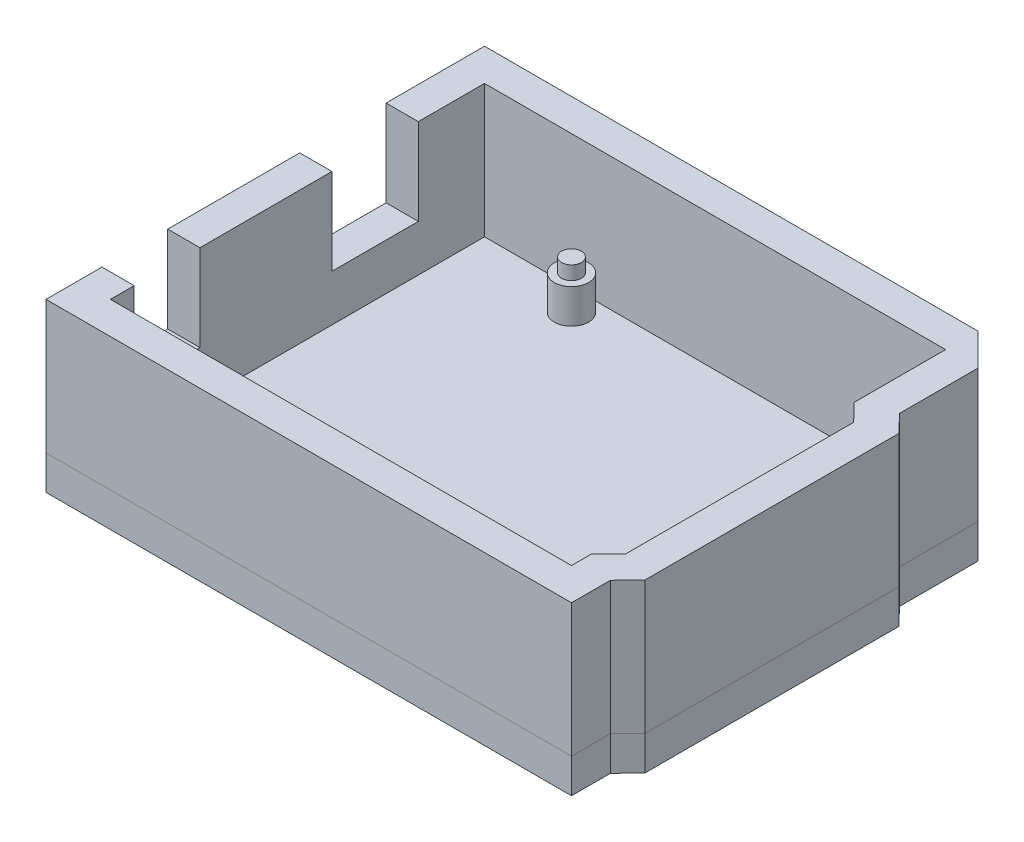
SolidWorks part; units mm, degrees
ref_plane "Front Plane" through (0, 0, 0) normal (0, 0, 1) x (1, 0, 0)
ref_plane "Top Plane" through (0, 0, 0) normal (0, 1, 0) x (1, 0, 0)
ref_plane "Right Plane" through (0, 0, 0) normal (1, 0, 0) x (0, 0, -1)
sketch "Sketch2" plane through (0, 0, 0) normal (0, 1, 0) x (1, 0, 0)
  line L3 (12.5897, 24.8031) -> (15.0697, 22.2631)
  line L4 (15.0697, 22.2631) -> (15.0697, -10.5029)
  line L5 (15.0697, -10.5029) -> (12.5897, -13.0429)
  line L6 (12.5897, -13.0429) -> (12.5897, -15.5829)
  line L7 (12.5897, -15.5829) -> (-53.4803, -15.5829)
  line L8 (-53.4803, -15.5829) -> (-53.4803, 37.7956)
  line L9 (-58.7803, 43.0956) -> (13.2202, 43.0956)
  line L10 (13.2202, 43.0956) -> (17.8897, 38.4261)
  line L11 (17.8897, 38.4261) -> (17.8897, 26.9614)
  line L12 (17.8897, 26.9614) -> (20.3697, 24.4214)
  line L13 (20.3697, 24.4214) -> (20.3697, -12.6612)
  line L14 (20.3697, -12.6612) -> (17.8897, -15.2012)
  line L15 (17.8897, -15.2012) -> (17.8897, -20.8829)
  line L16 (17.8897, -20.8829) -> (-58.7803, -20.8829)
  line L17 (-58.7803, -20.8829) -> (-58.7803, 43.0956)
  line L20 (12.5897, 37.7956) -> (12.5897, 24.8031)
  line L21 (11.0249, 37.7956) -> (12.5897, 36.2308) construction
  line L26 (12.5897, 36.2308) -> (12.5897, 24.8031) construction
  line L27 (-53.4803, 37.7956) -> (11.0249, 37.7956) construction
  line L28 (12.5897, 37.7956) -> (-53.4803, 37.7956)
  circle A0 centre (-38.2103, 35.2171) radius 1.5875
  circle A1 centre (12.5579, 19.9653) radius 1.5875
  circle A2 centre (12.5897, -7.9629) radius 1.5875
  circle A3 centre (-39.5103, -13.0429) radius 1.5875
  dimension "D4" = 3.5499
  dimension "D5" = 32.766
  dimension "D6" = 3.5499
  dimension "D7" = 2.54
  dimension "D8" = 66.07
  dimension "D9" = 53.3785
  dimension "D11" = 135.685
  dimension "D12" = 5.3
extrude "Boss-Extrude1" add sketch "Sketch2" along normal blind 5 contours L17 L16 L15 L14 L13 L12 L11 L10 L9 L7 L8 L3 L4 L5 L6 | L8 L7 L6 L5 L4 L3 A3 A2 A1 A0 region at (-19.6729, 0, -11.0012) region at (-22.7801, 0, -42.0778)
sketch "Sketch4" plane through (0, 5, 0) normal (0, 1, 0) x (1, 0, 0)
  line L3 (12.5885, 24.8065) -> (15.0685, 22.2665)
  line L4 (15.0685, 22.2665) -> (15.0685, -10.4995)
  line L5 (15.0685, -10.4995) -> (12.5885, -13.0395)
  line L6 (12.5885, -13.0395) -> (12.5885, -15.5795)
  line L7 (12.5885, -15.5795) -> (-53.4815, -15.5795)
  line L8 (-53.4815, -15.5795) -> (-53.4815, 37.799)
  line L9 (-58.7815, 43.099) -> (13.2191, 43.099)
  line L10 (13.2191, 43.099) -> (17.8885, 38.4295)
  line L11 (17.8885, 38.4295) -> (17.8885, 26.9649)
  line L12 (17.8885, 26.9649) -> (20.3685, 24.4249)
  line L13 (20.3685, 24.4249) -> (20.3685, -12.6578)
  line L14 (20.3685, -12.6578) -> (17.8885, -15.1978)
  line L15 (17.8885, -15.1978) -> (17.8885, -20.8795)
  line L16 (17.8885, -20.8795) -> (-58.7815, -20.8795)
  line L17 (-58.7815, -20.8795) -> (-58.7815, 43.099)
  line L21 (13.1885, 25.0509) -> (15.6685, 22.5109)
  line L22 (15.6685, 22.5109) -> (15.6685, -10.7438)
  line L23 (15.6685, -10.7438) -> (13.1885, -13.2838)
  line L24 (13.1885, -13.2838) -> (13.1885, -16.1795)
  line L25 (13.1885, -16.1795) -> (-54.0815, -16.1795)
  line L26 (-54.0815, -16.1795) -> (-54.0815, 38.399)
  line L31 (13.1885, 38.399) -> (13.1885, 25.0509)
  line L32 (11.2723, 38.399) -> (13.1885, 36.4827) construction
  line L33 (11.0238, 37.799) -> (12.5885, 36.2342) construction
  line L42 (13.1885, 36.4827) -> (13.1885, 25.0509) construction
  line L43 (-54.0815, 38.399) -> (11.2723, 38.399) construction
  line L44 (-53.4815, 37.799) -> (11.0238, 37.799) construction
  line L45 (12.5885, 36.2342) -> (12.5885, 24.8065) construction
  line L46 (12.5885, 24.8065) -> (12.5897, 37.7956)
  line L47 (12.5897, 37.7956) -> (-53.4815, 37.799)
  line L48 (-54.0815, 38.399) -> (13.1885, 38.399)
  circle A0 centre (-38.2115, 35.2205) radius 1.5875
  circle A1 centre (12.5567, 19.9688) radius 1.5875
  circle A2 centre (12.5885, -7.9595) radius 1.5875
  circle A3 centre (-39.5115, -13.0395) radius 1.5875
  dimension "D3" = 3.5499
  dimension "D4" = 32.766
  dimension "D5" = 3.5499
  dimension "D6" = 2.54
  dimension "D7" = 66.07
  dimension "D8" = 53.3785
  dimension "D10" = 135.685
  dimension "D11" = 0.6
extrude "Boss-Extrude3" add sketch "Sketch4" along normal blind 10 contours L9 L10 L11 L12 L13 L14 L15 L16 L17 | L21 L22 L23 L24 L25 L26 L48 L31
sketch "Sketch5" plane through (0, 15, 0) normal (0, 1, 0) x (1, 0, 0)
  line L0 (-58.7815, -20.8795) -> (-58.7815, 43.099) construction
  line L7 (-54.0815, -16.1795) -> (-54.0815, 38.399) construction
  line L14 (-58.7815, 28.439) -> (-58.7815, 16.439)
  line L16 (-54.0815, 28.439) -> (-54.0815, 16.439)
  line L17 (-54.0815, -16.1795) -> (-54.0815, 38.399) construction
  line L37 (-58.7815, 28.439) -> (-58.7815, 28.739)
  line L38 (-58.7815, 28.739) -> (-54.0815, 28.739)
  line L39 (-54.0815, 28.439) -> (-54.0815, 28.739)
  line L41 (-58.7815, 16.439) -> (-58.7815, 16.139)
  line L42 (-58.7815, 16.139) -> (-54.0815, 16.139)
  line L43 (-54.0815, 16.439) -> (-54.0815, 16.139)
  line L49 (-58.7815, -3.421) -> (-58.7815, -12.4107)
  line L59 (-54.0815, -3.421) -> (-54.0815, -12.4107)
  line L60 (-58.7815, -12.4107) -> (-58.7815, -12.7107)
  line L62 (-58.7815, -3.421) -> (-58.7815, -3.121)
  line L63 (-58.7815, -3.121) -> (-54.0815, -3.121)
  line L64 (-54.0815, -3.421) -> (-54.0815, -3.121)
  line L69 (-58.7815, -12.7107) -> (-54.0815, -12.7107)
  line L70 (-54.0815, -12.7107) -> (-54.0815, -12.4107)
  line L71 (-58.7815, -12.4107) -> (-58.7815, -12.7107)
  line M14 (-58.7815, 43.099) -> (-58.7815, -20.8795)
  line M32 (-54.0815, -16.1795) -> (-54.0815, 38.399)
  dimension "D1" = 0.3
  dimension "D2" = 12
  dimension "D3" = 0.3
  dimension "D4" = 0.3
  dimension "D6" = 0.3
extrude "Cut-Extrude1" cut sketch "Sketch5" against normal blind 3.22 contours L42 L38 M14 M32 | M32 M14 region at (-56.4315, 15, -22.439) region at (-56.4315, 15, 7.9158)
sketch "Sketch8" plane through (0, 15, 0) normal (0, 1, 0) x (1, 0, 0)
  line L1 (-54.0815, -16.1795) -> (-54.0815, -12.7107)
  line L11 (-58.7815, 16.139) -> (-54.0815, 16.139)
  line L17 (-58.7815, 16.139) -> (-58.7815, -3.121)
  line L18 (-58.7815, -3.121) -> (-54.0815, -3.121)
  line L20 (-54.0815, 16.139) -> (-54.0815, -3.121)
  line L30 (-54.0815, -12.7107) -> (-58.7815, -12.7107)
  line L31 (-58.7815, -12.7107) -> (-58.7815, -20.8795)
  line L62 (15.6685, 22.5109) -> (15.6685, -10.7438)
  line L63 (15.6685, -10.7438) -> (13.1885, -13.2838)
  line L64 (13.1885, -13.2838) -> (13.1885, -16.1795)
  line L65 (13.1885, -16.1795) -> (-54.0815, -16.1795)
  line L66 (-54.0815, -16.1795) -> (-54.0815, -12.7107) construction
  line L67 (-54.0815, -16.1795) -> (-54.0815, 38.399) construction
  line L71 (-58.7815, -20.8795) -> (17.8885, -20.8795)
  line L72 (17.8885, -20.8795) -> (17.8885, -15.1978)
  line L73 (17.8885, -15.1978) -> (20.3685, -12.6578)
  line L74 (20.3685, -12.6578) -> (20.3685, 24.4249)
  line L75 (20.3685, 24.4249) -> (17.8885, 26.9649)
  line L76 (17.8885, 26.9649) -> (17.8885, 38.4295)
  line L77 (17.8885, 38.4295) -> (13.2191, 43.099)
  line L78 (13.2191, 43.099) -> (-58.7815, 43.099)
  line L79 (-58.7815, 43.099) -> (-58.7815, 28.739)
  line L80 (-58.7815, 28.739) -> (-54.0815, 28.739)
  line L106 (-54.0815, 28.739) -> (-54.0815, 38.399)
  line L107 (-54.0815, 38.399) -> (13.1885, 38.399)
  line L109 (13.1885, 38.399) -> (13.1885, 25.0509)
  line L110 (13.1885, 25.0509) -> (15.6685, 22.5109)
extrude "Boss-Extrude4" add sketch "Sketch8" along normal blind 9.39
sketch "Sketch9" plane through (0, 5, 0) normal (0, 1, 0) x (1, 0, 0)
  circle A0 centre (-38.2103, 35.2171) radius 2.5
  circle A1 centre (12.5579, 19.9653) radius 2.5
  circle A2 centre (12.5897, -7.9629) radius 2.5
  circle A3 centre (-39.5103, -13.0429) radius 2.5
  dimension "D1" = 5
  dimension "D2" = 5
  dimension "D3" = 5
  dimension "D4" = 5
extrude "Boss-Extrude5" add sketch "Sketch9" along normal blind 5
sketch "Sketch10" plane through (0, 10, 0) normal (0, 1, 0) x (1, 0, 0)
  circle A0 centre (-38.2103, 35.2171) radius 1.44
  circle A1 centre (12.5579, 19.9653) radius 1.425
  circle A2 centre (12.5897, -7.9629) radius 1.425
  circle A3 centre (-39.5103, -13.0429) radius 1.425
  dimension "D1" = 2.88
  dimension "D2" = 2.85
  dimension "D3" = 2.85
  dimension "D4" = 2.85
extrude "Boss-Extrude6" add sketch "Sketch10" along normal blind 2
sketch "Sketch11" plane through (0, 11.78, 0) normal (0, 1, 0) x (1, 0, 0)
  line L5 (-58.7815, -3.121) -> (-54.0815, -3.121)
  line L6 (-58.7815, -3.121) -> (-58.7815, -12.7107)
  line L7 (-58.7815, -12.7107) -> (-54.0815, -12.7107)
  line L8 (-54.0815, -3.121) -> (-54.0815, -12.7107)
extrude "Cut-Extrude2" cut sketch "Sketch11" against normal blind 0.01
